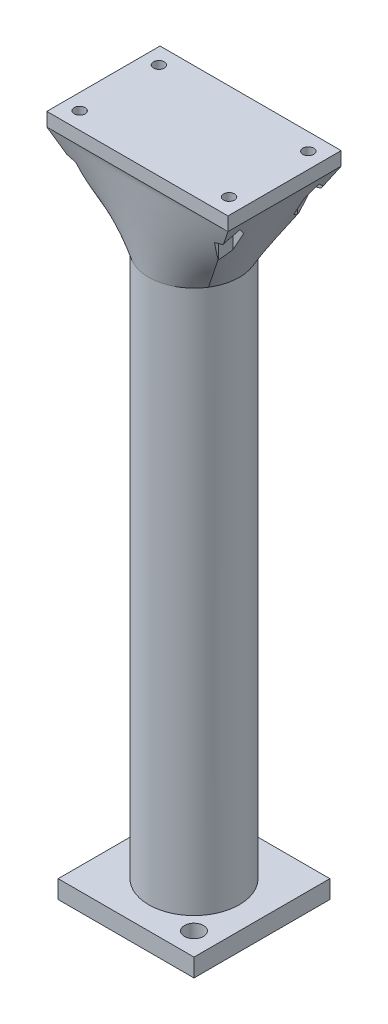
SolidWorks part; units mm, degrees
ref_plane "Front Plane" through (0, 0, 0) normal (0, 0, 1) x (1, 0, 0)
ref_plane "Top Plane" through (0, 0, 0) normal (0, 1, 0) x (1, 0, 0)
ref_plane "Right Plane" through (0, 0, 0) normal (1, 0, 0) x (0, 0, -1)
sketch "Sketch1" plane through (0, 0, 0) normal (0, 1, 0) x (1, 0, 0)
  line L1 (-15, 15) -> (15, 15)
  line L2 (-15, 15) -> (-15, -15)
  line L3 (-15, -15) -> (15, -15)
  line L4 (15, 15) -> (15, -15)
  line L5 (-15, 15) -> (15, -15) construction
  line L6 (-15, -15) -> (15, 15) construction
  point P0 (0, 0)
  dimension "D1" = 30
extrude "Boss-Extrude1" add sketch "Sketch1" along normal blind 4 contours L1 L4 L3 L2
sketch "Sketch2" plane through (0, 4, 0) normal (0, 1, 0) x (1, 0, 0)
  line L1 (-10, -10) -> (10, -10) construction
  line L2 (-10, -10) -> (-10, 10) construction
  line L3 (-10, 10) -> (10, 10) construction
  line L4 (10, -10) -> (10, 10) construction
  line L5 (-10, -10) -> (10, 10) construction
  line L6 (-10, 10) -> (10, -10) construction
  circle A0 centre (-10, 10) radius 2.1
  circle A1 centre (10, -10) radius 2.1
  point P0 (0, 0)
  dimension "D2" = 4.2
  dimension "D1" = 20
extrude "Cut-Extrude1" cut sketch "Sketch2" against normal through all
sketch "Sketch3" plane through (0, 4, 0) normal (0, 1, 0) x (1, 0, 0)
  circle A0 centre (0, 0) radius 10
  dimension "D1" = 20
extrude "Boss-Extrude2" add sketch "Sketch3" along normal blind 120
ref_plane "Plane1" through (0, 144, 0) normal (0, 1, 0) x (1, 0, 0)
sketch "Sketch4" plane through (0, 144, 0) normal (0, 1, 0) x (1, 0, 0)
  line L1 (-20, -12.5) -> (20, -12.5)
  line L2 (-20, -12.5) -> (-20, 12.5)
  line L3 (-20, 12.5) -> (20, 12.5)
  line L4 (20, -12.5) -> (20, 12.5)
  line L5 (-20, -12.5) -> (20, 12.5) construction
  line L6 (-20, 12.5) -> (20, -12.5) construction
  point P0 (0, 0)
  dimension "D1" = 40
  dimension "D2" = 25
sketch "Sketch5" plane through (0, 124, 0) normal (0, 1, 0) x (1, 0, 0)
  circle A0 centre (0, 0) radius 10 construction
  circle A1 centre (0, 0) radius 10
loft "Loft1" add profiles "Sketch5", "Sketch4" connector at (-5.9538, 124, -8.0344) connector at (-20, 144, 12.5)
extrude "Boss-Extrude3" add sketch "Sketch4<2>" along normal blind 3
sketch "Sketch4<2>" plane through (0, 144, 0) normal (0, 1, 0) x (1, 0, 0) same geometry as "Sketch4"
sketch "Sketch7" plane through (0, 147, 0) normal (0, 1, 0) x (1, 0, 0)
  line L1 (-16.5, -8.75) -> (16.5, -8.75) construction
  line L2 (-16.5, -8.75) -> (-16.5, 8.75) construction
  line L3 (-16.5, 8.75) -> (16.5, 8.75) construction
  line L4 (16.5, -8.75) -> (16.5, 8.75) construction
  line L5 (-16.5, -8.75) -> (16.5, 8.75) construction
  line L6 (-16.5, 8.75) -> (16.5, -8.75) construction
  circle A0 centre (-16.5, 8.75) radius 1.2
  circle A1 centre (-16.5, -8.75) radius 1.2
  circle A2 centre (16.5, 8.75) radius 1.2
  circle A3 centre (16.5, -8.75) radius 1.2
  point P0 (0, 0)
  dimension "D3" = 2.4
  dimension "D1" = 33
  dimension "D2" = 17.5
extrude "Cut-Extrude2" cut sketch "Sketch7" against normal blind 30
sketch "Sketch8" plane through (0, 144, 0) normal (0, 1, 0) x (1, 0, 0)
  line L1 (-17.6836, 6.7) -> (-15.3164, 6.7)
  line L2 (-15.3164, 6.7) -> (-14.1329, 8.75)
  line L3 (-14.1329, 8.75) -> (-15.3164, 10.8)
  line L4 (-15.3164, 10.8) -> (-17.6836, 10.8)
  line L5 (-17.6836, 10.8) -> (-18.8671, 8.75)
  line L6 (-18.8671, 8.75) -> (-17.6836, 6.7)
  line L7 (-15.3164, -6.7) -> (-17.6836, -6.7)
  line L8 (-17.6836, -6.7) -> (-18.8671, -8.75)
  line L9 (-18.8671, -8.75) -> (-17.6836, -10.8)
  line L10 (-17.6836, -10.8) -> (-15.3164, -10.8)
  line L11 (-15.3164, -10.8) -> (-14.1329, -8.75)
  line L12 (-14.1329, -8.75) -> (-15.3164, -6.7)
  line L13 (15.3164, 6.7) -> (17.6836, 6.7)
  line L14 (17.6836, 6.7) -> (18.8671, 8.75)
  line L15 (18.8671, 8.75) -> (17.6836, 10.8)
  line L16 (17.6836, 10.8) -> (15.3164, 10.8)
  line L17 (15.3164, 10.8) -> (14.1329, 8.75)
  line L18 (14.1329, 8.75) -> (15.3164, 6.7)
  line L19 (14.1329, -8.75) -> (15.3164, -10.8)
  line L20 (15.3164, -10.8) -> (17.6836, -10.8)
  line L21 (17.6836, -10.8) -> (18.8671, -8.75)
  line L22 (18.8671, -8.75) -> (17.6836, -6.7)
  line L23 (17.6836, -6.7) -> (15.3164, -6.7)
  line L24 (15.3164, -6.7) -> (14.1329, -8.75)
  circle A0 centre (-16.5, 8.75) radius 2.05 construction
  circle A1 centre (-16.5, -8.75) radius 2.05 construction
  circle A2 centre (16.5, 8.75) radius 2.05 construction
  circle A3 centre (16.5, -8.75) radius 2.05 construction
  dimension "D1" = 4.1
extrude "Cut-Extrude3" cut sketch "Sketch8" against normal blind 30
